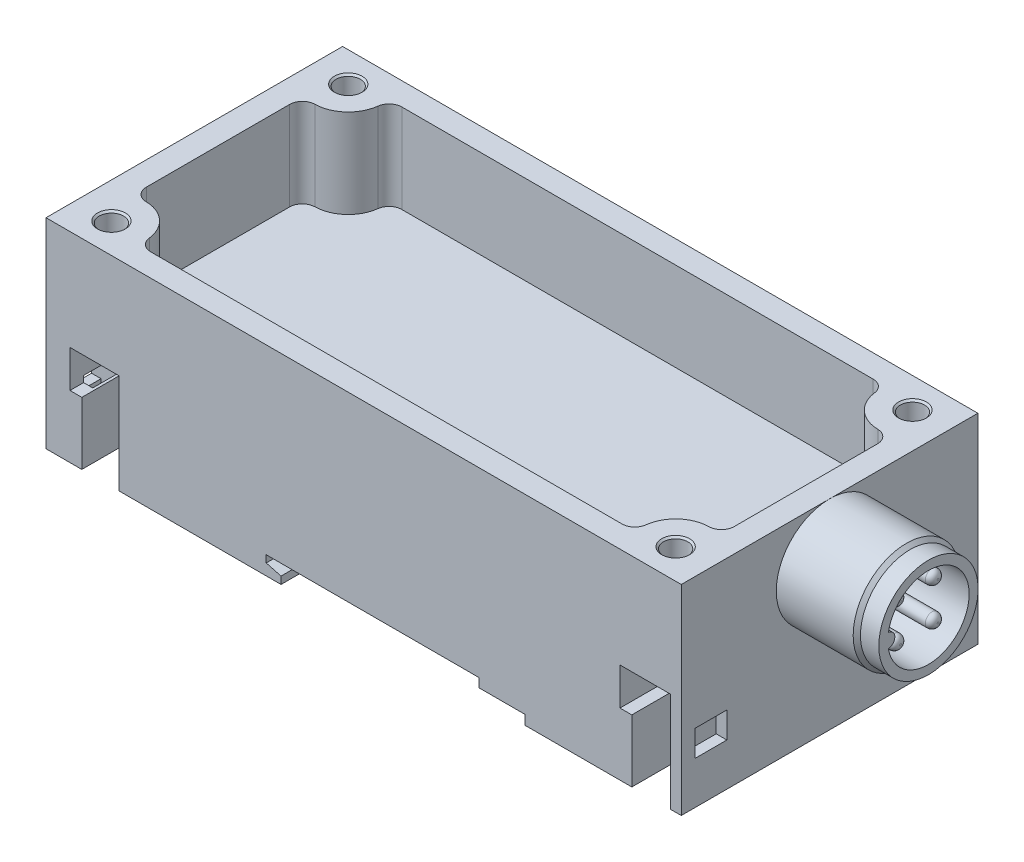
SolidWorks part; units mm, degrees
ref_plane "Front Plane" through (0, 0, 0) normal (0, 0, 1) x (1, 0, 0)
ref_plane "Top Plane" through (0, 0, 0) normal (0, 1, 0) x (1, 0, 0)
ref_plane "Right Plane" through (0, 0, 0) normal (1, 0, 0) x (0, 0, -1)
ref_plane "Plane1" through (0, 0, 0) normal (0, 0, 1) x (1, 0, 0)
sketch "Sketch1" plane through (0, 0, 0) normal (0, 0, 1) x (1, 0, 0)
  line L0 (-53.65, 33.8) -> (-53.65, 0)
  line L1 (-53.65, 0) -> (-47.6, 0)
  line L2 (-47.6, 0) -> (-47.6, 10.55)
  line L3 (-47.6, 10.55) -> (-49.6, 10.55)
  line L4 (-49.6, 10.55) -> (-49.6, 16.85)
  line L5 (-49.6, 16.85) -> (-41.3, 16.85)
  line L6 (-41.3, 16.85) -> (-41.3, 0)
  line L7 (-41.3, 0) -> (-13.95, 0)
  line L8 (-13.95, 0) -> (-13.95, 1.2301)
  line L9 (-13.95, 1.2301) -> (-16.45, 1.9)
  line L10 (-16.45, 1.9) -> (-16.45, 3.1)
  line L11 (-16.45, 3.1) -> (19.45, 3.1)
  line L12 (19.45, 3.1) -> (19.45, 1.6)
  line L13 (19.45, 1.6) -> (27.25, 1.6)
  line L14 (27.25, 1.6) -> (27.25, 0)
  line L15 (27.25, 0) -> (45.3, 0)
  line L16 (45.3, 0) -> (45.3, 10.55)
  line L17 (45.3, 10.55) -> (43.3, 10.55)
  line L18 (43.3, 10.55) -> (43.3, 16.85)
  line L19 (43.3, 16.85) -> (51.85, 16.85)
  line L20 (51.85, 16.85) -> (51.85, 0)
  line L21 (51.85, 0) -> (53.65, 0)
  line L22 (53.65, 0) -> (53.65, 33.8)
  line L23 (53.65, 33.8) -> (-53.65, 33.8)
extrude "Boss-Extrude1" add sketch "Sketch1" against normal blind 25.05 and the other way blind 25.05
ref_plane "Plane2" through (0, 0, 20) normal (0, 0, 1) x (1, 0, 0)
sketch "Sketch2" plane through (0, 0, 20) normal (0, 0, 1) x (1, 0, 0)
  line L0 (47.65, 33.8) -> (50, 33.8)
  line L1 (50, 33.8) -> (49.7, 33.5)
  line L2 (49.7, 33.5) -> (49.7, 26.6)
  line L3 (49.5, 26.4) -> (49.02, 26.4)
  line L4 (49.02, 26.4) -> (48.95, 18.4)
  line L5 (48.95, 18.4) -> (47.65, 18.4)
  line L6 (47.65, 18.4) -> (47.65, 33.8)
  line L7 (47.65, 18.4) -> (47.65, 33.8) construction
  arc A0 (49.7, 26.6) -> (49.5, 26.4) centre (49.5, 26.6) cw
revolve "Cut-Revolve1" cut sketch "Sketch2" angle 360 about L7 reverse direction yes
ref_plane "Plane3" through (0, 0, -20) normal (0, 0, 1) x (1, 0, 0)
sketch "Sketch3" plane through (0, 0, -20) normal (0, 0, 1) x (1, 0, 0)
  line L0 (47.65, 33.8) -> (50, 33.8)
  line L1 (50, 33.8) -> (49.7, 33.5)
  line L2 (49.7, 33.5) -> (49.7, 26.6)
  line L3 (49.5, 26.4) -> (49.02, 26.4)
  line L4 (49.02, 26.4) -> (48.95, 18.4)
  line L5 (48.95, 18.4) -> (47.65, 18.4)
  line L6 (47.65, 18.4) -> (47.65, 33.8)
  line L7 (47.65, 18.4) -> (47.65, 33.8) construction
  arc A0 (49.7, 26.6) -> (49.5, 26.4) centre (49.5, 26.6) cw
revolve "Cut-Revolve2" cut sketch "Sketch3" angle 360 about L7 reverse direction yes
ref_plane "Plane4" through (0, 0, -20) normal (0, 0, 1) x (1, 0, 0)
sketch "Sketch4" plane through (0, 0, -20) normal (0, 0, 1) x (1, 0, 0)
  line L0 (-47.65, 33.8) -> (-45.3, 33.8)
  line L1 (-45.3, 33.8) -> (-45.6, 33.5)
  line L2 (-45.6, 33.5) -> (-45.6, 26.6)
  line L3 (-45.8, 26.4) -> (-46.28, 26.4)
  line L4 (-46.28, 26.4) -> (-46.35, 18.4)
  line L5 (-46.35, 18.4) -> (-47.65, 18.4)
  line L6 (-47.65, 18.4) -> (-47.65, 33.8)
  line L7 (-47.65, 18.4) -> (-47.65, 33.8) construction
  arc A0 (-45.6, 26.6) -> (-45.8, 26.4) centre (-45.8, 26.6) cw
revolve "Cut-Revolve3" cut sketch "Sketch4" angle 360 about L7 reverse direction yes
ref_plane "Plane5" through (0, 0, 20) normal (0, 0, 1) x (1, 0, 0)
sketch "Sketch5" plane through (0, 0, 20) normal (0, 0, 1) x (1, 0, 0)
  line L0 (-47.65, 33.8) -> (-45.3, 33.8)
  line L1 (-45.3, 33.8) -> (-45.6, 33.5)
  line L2 (-45.6, 33.5) -> (-45.6, 26.6)
  line L3 (-45.8, 26.4) -> (-46.28, 26.4)
  line L4 (-46.28, 26.4) -> (-46.35, 18.4)
  line L5 (-46.35, 18.4) -> (-47.65, 18.4)
  line L6 (-47.65, 18.4) -> (-47.65, 33.8)
  line L7 (-47.65, 18.4) -> (-47.65, 33.8) construction
  arc A0 (-45.6, 26.6) -> (-45.8, 26.4) centre (-45.8, 26.6) cw
revolve "Cut-Revolve4" cut sketch "Sketch5" angle 360 about L7 reverse direction yes
ref_plane "Plane6" through (0, 33.8, 0) normal (0, 1, 0) x (1, 0, 0)
sketch "Sketch6" plane through (0, 33.8, 0) normal (0, 1, 0) x (1, 0, 0)
  line L0 (-39.8073, -21.2) -> (39.8073, -21.2)
  line L1 (49.65, -12.1014) -> (49.65, 12.1014)
  line L2 (39.8073, 21.2) -> (-39.8073, 21.2)
  line L3 (-49.65, 12.1014) -> (-49.65, -12.1014)
  arc A0 (-49.65, -12.1014) -> (-47.5408, -14.251) centre (-47.5, -12.1014) ccw
  arc A1 (-47.5408, -14.251) -> (-41.9417, -19.3085) centre (-47.65, -20) cw
  arc A2 (-41.9417, -19.3085) -> (-39.8073, -21.2) centre (-39.8073, -19.05) ccw
  arc A3 (39.8073, -21.2) -> (41.9417, -19.3085) centre (39.8073, -19.05) ccw
  arc A4 (41.9417, -19.3085) -> (47.5408, -14.251) centre (47.65, -20) cw
  arc A5 (47.5408, -14.251) -> (49.65, -12.1014) centre (47.5, -12.1014) ccw
  arc A6 (49.65, 12.1014) -> (47.5408, 14.251) centre (47.5, 12.1014) ccw
  arc A7 (47.5408, 14.251) -> (41.9417, 19.3085) centre (47.65, 20) cw
  arc A8 (41.9417, 19.3085) -> (39.8073, 21.2) centre (39.8073, 19.05) ccw
  arc A9 (-39.8073, 21.2) -> (-41.9417, 19.3085) centre (-39.8073, 19.05) ccw
  arc A10 (-41.9417, 19.3085) -> (-47.5408, 14.251) centre (-47.65, 20) cw
  arc A11 (-47.5408, 14.251) -> (-49.65, 12.1014) centre (-47.5, 12.1014) ccw
extrude "Cut-Extrude1" cut sketch "Sketch6" against normal blind 15
ref_plane "Plane7" through (53.65, 0, 0) normal (1, 0, 0) x (0, 0, -1)
sketch "Sketch7" plane through (53.65, 0, 0) normal (1, 0, 0) x (0, 0, -1)
  line L0 (17.35, 7.2) -> (22.75, 7.2)
  line L1 (22.75, 7.2) -> (22.75, 11.6)
  line L2 (22.75, 11.6) -> (17.35, 11.6)
  line L3 (17.35, 11.6) -> (17.35, 7.2)
extrude "Cut-Extrude2" cut sketch "Sketch7" against normal blind 3
ref_plane "Plane8" through (53.65, 0, 0) normal (1, 0, 0) x (0, 0, -1)
sketch "Sketch8" plane through (53.65, 0, 0) normal (1, 0, 0) x (0, 0, -1)
  line L0 (-22.75, 7.2) -> (-17.35, 7.2)
  line L1 (-17.35, 7.2) -> (-17.35, 11.6)
  line L2 (-17.35, 11.6) -> (-22.75, 11.6)
  line L3 (-22.75, 11.6) -> (-22.75, 7.2)
extrude "Cut-Extrude3" cut sketch "Sketch8" against normal blind 3
ref_plane "Plane9" through (-53.65, 0, 0) normal (1, 0, 0) x (0, 0, -1)
sketch "Sketch9" plane through (-53.65, 0, 0) normal (1, 0, 0) x (0, 0, -1)
  line L0 (17.35, 7.2) -> (22.75, 7.2)
  line L1 (22.75, 7.2) -> (22.75, 11.6)
  line L2 (22.75, 11.6) -> (17.35, 11.6)
  line L3 (17.35, 11.6) -> (17.35, 7.2)
extrude "Cut-Extrude4" cut sketch "Sketch9" along normal blind 5
ref_plane "Plane10" through (-53.65, 0, 0) normal (1, 0, 0) x (0, 0, -1)
sketch "Sketch10" plane through (-53.65, 0, 0) normal (1, 0, 0) x (0, 0, -1)
  line L0 (-22.75, 7.2) -> (-17.35, 7.2)
  line L1 (-17.35, 7.2) -> (-17.35, 11.6)
  line L2 (-17.35, 11.6) -> (-22.75, 11.6)
  line L3 (-22.75, 11.6) -> (-22.75, 7.2)
extrude "Cut-Extrude5" cut sketch "Sketch10" along normal blind 5
ref_plane "Plane11" through (0, 0, 0) normal (0, 0, 1) x (1, 0, 0)
sketch "Sketch11" plane through (0, 0, 0) normal (0, 0, 1) x (1, 0, 0)
  line L0 (53.65, 24.8) -> (53.65, 33.8)
  line L1 (53.65, 33.8) -> (66.6365, 33.8)
  line L2 (66.6365, 33.8) -> (67.25, 33.1865)
  line L3 (67.25, 33.1865) -> (70.35, 33.1865)
  line L4 (70.35, 33.1865) -> (70.35, 31.675)
  line L5 (70.35, 31.675) -> (55.85, 31.675)
  line L6 (55.85, 31.675) -> (55.85, 24.8)
  line L7 (55.85, 24.8) -> (53.65, 24.8)
  line L8 (70.35, 24.8) -> (53.65, 24.8) construction
revolve "Revolve1" add sketch "Sketch11" angle 360 about L8 reverse direction yes
cosmetic thread "Cosmetic Thread1" parameters "D1"=13.6, "D2"=16.773
ref_plane "Plane12" through (53.65, 0, 0) normal (1, 0, 0) x (0, 0, -1)
sketch "Sketch12" plane through (53.65, 0, 0) normal (1, 0, 0) x (0, 0, -1)
  arc A0 (-6.7703, 25.9954) -> (-6.7703, 23.6046) centre (0, 24.8) ccw
  arc A1 (-6.7703, 23.6046) -> (-6.7703, 25.9954) centre (-6.875, 24.8) ccw
extrude "Boss-Extrude2" add sketch "Sketch12" along normal blind 16.7
ref_plane "Plane13" through (0, 0, -3.18) normal (0, 0, 1) x (1, 0, 0)
sketch "Sketch13" plane through (0, 0, -3.18) normal (0, 0, 1) x (1, 0, 0)
  line L0 (53.65, 27.98) -> (53.65, 29.14)
  line L1 (53.65, 29.14) -> (67.8, 29.14)
  line L2 (68.8, 28.14) -> (68.8, 27.98)
  line L3 (68.8, 27.98) -> (53.65, 27.98)
  line L4 (68.8, 27.98) -> (53.65, 27.98) construction
  arc A0 (67.8, 29.14) -> (68.8, 28.14) centre (67.8, 28.14) cw
revolve "Revolve2" add sketch "Sketch13" angle 360 about L4 reverse direction yes
ref_plane "Plane14" through (0, 0, 3.18) normal (0, 0, 1) x (1, 0, 0)
sketch "Sketch14" plane through (0, 0, 3.18) normal (0, 0, 1) x (1, 0, 0)
  line L0 (53.65, 27.98) -> (53.65, 29.14)
  line L1 (53.65, 29.14) -> (67.8, 29.14)
  line L2 (68.8, 28.14) -> (68.8, 27.98)
  line L3 (68.8, 27.98) -> (53.65, 27.98)
  line L4 (68.8, 27.98) -> (53.65, 27.98) construction
  arc A0 (67.8, 29.14) -> (68.8, 28.14) centre (67.8, 28.14) cw
revolve "Revolve3" add sketch "Sketch14" angle 360 about L4 reverse direction yes
ref_plane "Plane15" through (0, 0, -3.18) normal (0, 0, 1) x (1, 0, 0)
sketch "Sketch15" plane through (0, 0, -3.18) normal (0, 0, 1) x (1, 0, 0)
  line L0 (53.65, 21.62) -> (53.65, 22.78)
  line L1 (53.65, 22.78) -> (67.8, 22.78)
  line L2 (68.8, 21.78) -> (68.8, 21.62)
  line L3 (68.8, 21.62) -> (53.65, 21.62)
  line L4 (68.8, 21.62) -> (53.65, 21.62) construction
  arc A0 (67.8, 22.78) -> (68.8, 21.78) centre (67.8, 21.78) cw
revolve "Revolve4" add sketch "Sketch15" angle 360 about L4 reverse direction yes
ref_plane "Plane16" through (0, 0, 3.18) normal (0, 0, 1) x (1, 0, 0)
sketch "Sketch16" plane through (0, 0, 3.18) normal (0, 0, 1) x (1, 0, 0)
  line L0 (53.65, 21.62) -> (53.65, 22.78)
  line L1 (53.65, 22.78) -> (67.8, 22.78)
  line L2 (68.8, 21.78) -> (68.8, 21.62)
  line L3 (68.8, 21.62) -> (53.65, 21.62)
  line L4 (68.8, 21.62) -> (53.65, 21.62) construction
  arc A0 (67.8, 22.78) -> (68.8, 21.78) centre (67.8, 21.78) cw
revolve "Revolve5" add sketch "Sketch16" angle 360 about L4 reverse direction yes
ref_plane "Plane17" through (-52.05, 0, 0) normal (1, 0, 0) x (0, 0, -1)
sketch "Sketch17" plane through (-52.05, 0, 0) normal (1, 0, 0) x (0, 0, -1)
  line L0 (-22.75, 6.2) -> (-17.35, 6.2)
  line L1 (-17.35, 6.2) -> (-17.35, 11.6)
  line L2 (-17.35, 11.6) -> (-22.75, 11.6)
  line L3 (-22.75, 11.6) -> (-22.75, 6.2)
extrude "Cut-Extrude6" cut sketch "Sketch17" along normal blind 4
ref_plane "Plane18" through (-52.05, 0, 0) normal (1, 0, 0) x (0, 0, -1)
sketch "Sketch18" plane through (-52.05, 0, 0) normal (1, 0, 0) x (0, 0, -1)
  line L0 (17.35, 6.2) -> (22.75, 6.2)
  line L1 (22.75, 6.2) -> (22.75, 11.6)
  line L2 (22.75, 11.6) -> (17.35, 11.6)
  line L3 (17.35, 11.6) -> (17.35, 6.2)
extrude "Cut-Extrude7" cut sketch "Sketch18" along normal blind 4
